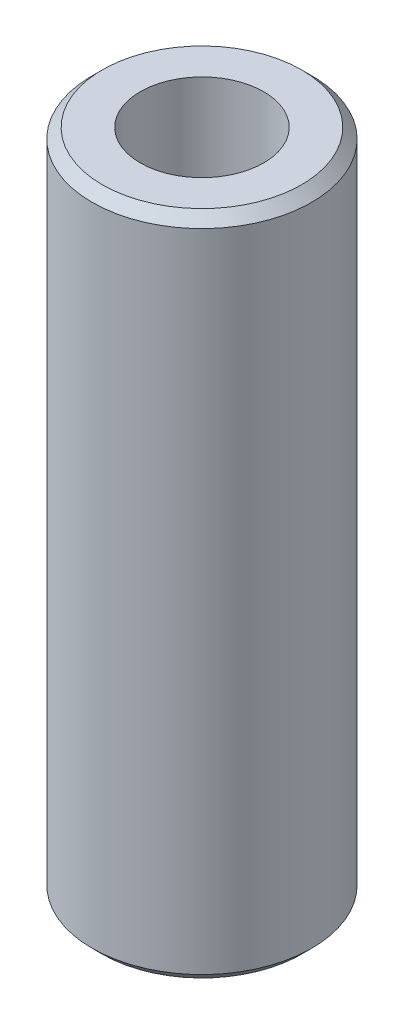
SolidWorks part; units mm, degrees
ref_plane "Front Plane" through (0, 0, 0) normal (0, 0, 1) x (1, 0, 0)
ref_plane "Top Plane" through (0, 0, 0) normal (0, 1, 0) x (1, 0, 0)
ref_plane "Right Plane" through (0, 0, 0) normal (1, 0, 0) x (0, 0, -1)
sketch "Sketch1" plane through (0, 0, 0) normal (0, 1, 0) x (1, 0, 0)
  circle A0 centre (0, 0) radius 47.5
  dimension "SHAFT_OD" = 95
extrude "Boss-Extrude1" add sketch "Sketch1" along normal blind 288.3931
sketch "Sketch2" plane through (0, 0, 0) normal (0, 1, 0) x (1, 0, 0)
  circle A0 centre (0, 0) radius 26.7205
  dimension "BORE_D" = 53.4409
extrude "Cut-Extrude1" cut sketch "Sketch2" along normal through all
chamfer "Chamfer1" distance 4.3953 angle 45 2 edges at (0, 288.3931, 47.5) (0, 0, 47.5)
